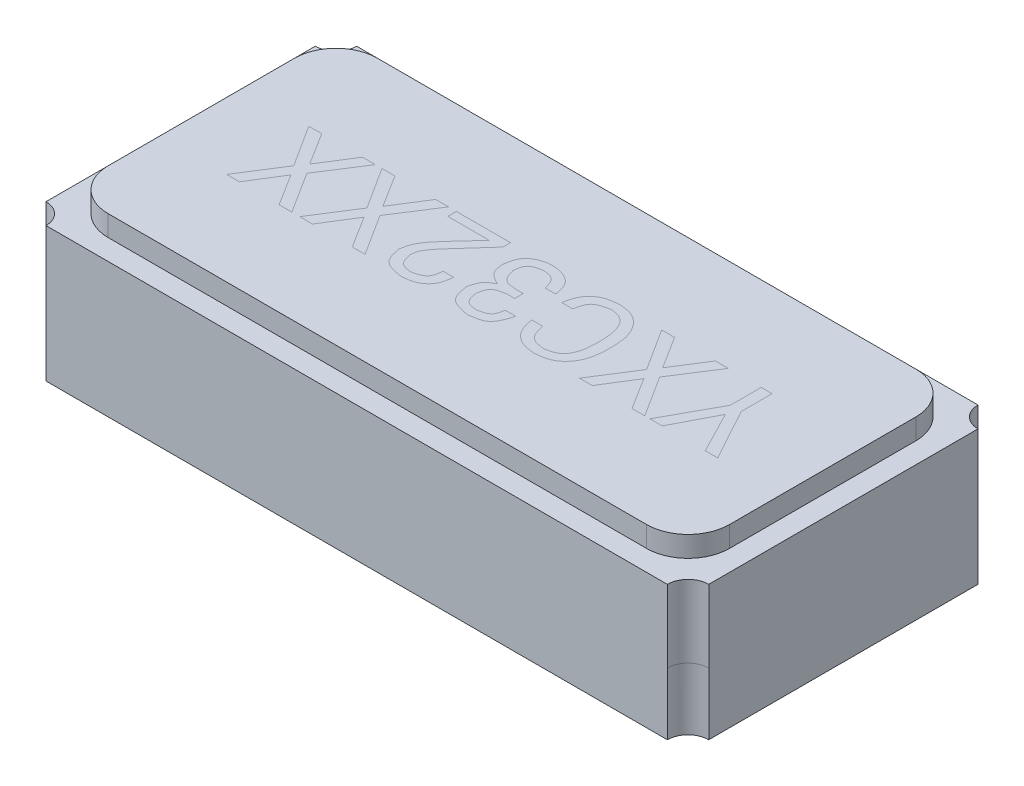
SolidWorks part; units mm, degrees
ref_plane "Спереди" through (0, 0, 0) normal (0, 0, 1) x (1, 0, 0)
ref_plane "Сверху" through (0, 0, 0) normal (0, 1, 0) x (1, 0, 0)
ref_plane "Справа" through (0, 0, 0) normal (1, 0, 0) x (0, 0, -1)
sketch "Эскиз1" plane through (0, 0, 0) normal (0, 1, 0) x (1, 0, 0)
  line L1 (-1.5, 0.75) -> (1.5, 0.75)
  line L2 (-1.6, 0.65) -> (-1.6, -0.65)
  line L3 (-1.5, -0.75) -> (1.5, -0.75)
  line L4 (1.6, 0.65) -> (1.6, -0.65)
  arc A0 (-1.6, 0.65) -> (-1.5, 0.75) centre (-1.6, 0.75) ccw
  arc A1 (1.5, 0.75) -> (1.6, 0.65) centre (1.6, 0.75) ccw
  arc A2 (-1.6, -0.65) -> (-1.5, -0.75) centre (-1.6, -0.75) cw
  arc A3 (1.5, -0.75) -> (1.6, -0.65) centre (1.6, -0.75) cw
  point P0 (0, 0)
  dimension "D3" = 0.1
  dimension "D1" = 3.2
  dimension "D2" = 1.5
  dimension "D4" = 1.6
  dimension "D5" = 0.75
extrude "Бобышка-Вытянуть1" add sketch "Эскиз1" along normal blind 0.65
sketch "Эскиз2" plane through (0, 0.65, 0) normal (0, 1, 0) x (1, 0, 0)
  line L0 (1.5, 0.75) -> (-1.5, 0.75) construction
  line L1 (-1.3, 0.65) -> (1.3, 0.65)
  line L2 (-1.5, 0.45) -> (-1.5, -0.45)
  line L3 (-1.3, -0.65) -> (1.3, -0.65)
  line L4 (1.5, 0.45) -> (1.5, -0.45)
  line L5 (-1.5, -0.75) -> (1.5, -0.75) construction
  line L6 (-1.6, 0.65) -> (-1.6, -0.65) construction
  line L7 (1.6, -0.65) -> (1.6, 0.65) construction
  arc A0 (1.3, -0.65) -> (1.5, -0.45) centre (1.3, -0.45) ccw
  arc A1 (1.3, 0.65) -> (1.5, 0.45) centre (1.3, 0.45) cw
  arc A2 (-1.5, -0.45) -> (-1.3, -0.65) centre (-1.3, -0.45) ccw
  arc A3 (-1.3, 0.65) -> (-1.5, 0.45) centre (-1.3, 0.45) ccw
  dimension "D1" = 0.2
  dimension "D2" = 0.1
  dimension "D3" = 0.1
  dimension "D4" = 0.1
  dimension "D5" = 0.1
extrude "Бобышка-Вытянуть2" add sketch "Эскиз2" along normal blind 0.1
sketch "Эскиз3" plane through (0, 0, 0) normal (0, -1, 0) x (1, 0, 0)
  line L0 (1.5, -0.75) -> (1.4, -0.65)
  line L1 (1.4, -0.65) -> (0.85, -0.65)
  line L2 (0.85, -0.65) -> (0.85, 0.35)
  line L3 (1.15, 0.65) -> (1.4, 0.65)
  line L4 (1.4, 0.65) -> (1.5, 0.75)
  line L5 (1.6, 0.65) -> (1.5, 0.55)
  line L6 (1.5, 0.55) -> (1.5, -0.55)
  line L7 (1.5, -0.55) -> (1.6, -0.65)
  line L8 (1.6, 0.65) -> (1.6, -0.65) construction
  line L9 (1.5, -0.75) -> (-1.5, -0.75) construction
  line L10 (-1.5, 0.75) -> (1.5, 0.75) construction
  line L11 (0, -0.75) -> (0, 0.75) construction
  line L12 (-1.5, -0.55) -> (-1.6, -0.65)
  line L13 (-1.5, 0.55) -> (-1.5, -0.55)
  line L14 (-1.6, 0.65) -> (-1.5, 0.55)
  line L15 (-1.4, 0.65) -> (-1.5, 0.75)
  line L16 (-0.85, 0.65) -> (-1.4, 0.65)
  line L17 (-0.85, -0.65) -> (-0.85, 0.65)
  line L18 (-1.4, -0.65) -> (-0.85, -0.65)
  line L19 (-1.5, -0.75) -> (-1.4, -0.65)
  line L20 (1.15, 0.65) -> (0.85, 0.35)
  arc A0 (1.5, 0.75) -> (1.6, 0.65) centre (1.6, 0.75) ccw
  arc A1 (1.6, -0.65) -> (1.5, -0.75) centre (1.6, -0.75) ccw
  arc A2 (1.6, -0.65) -> (1.5, -0.75) centre (1.6, -0.75) ccw construction
  arc A3 (1.5, 0.75) -> (1.6, 0.65) centre (1.6, 0.75) ccw construction
  arc A4 (-1.5, 0.75) -> (-1.6, 0.65) centre (-1.6, 0.75) cw
  arc A5 (-1.6, -0.65) -> (-1.5, -0.75) centre (-1.6, -0.75) cw
  dimension "D1" = 45
  dimension "D2" = 0.1
  dimension "D3" = 0.1
  dimension "D4" = 0.1
  dimension "D5" = 135
  dimension "D6" = 0.65
  dimension "D7" = 135
  dimension "D8" = 0.3
wrap "Перенос1" sketch "Эскиз3" wrap type scribe source sketch "Эскиз3"
sketch "Эскиз4" plane through (0, 0, -0.75) normal (0, 0, -1) x (-1, 0, 0)
  line L0 (-1.6, 0.3) -> (1.6, 0.3)
  line L1 (-1.6, 0.65) -> (-1.6, 0) construction
  line L2 (1.6, 0.65) -> (1.6, 0) construction
  line L3 (-1.5, 0) -> (1.5, 0) construction
  point P2 (0, 0)
  point P5 (0, 0)
  dimension "D1" = 0.3
split line "Разделяющая линия1"
sketch "Эскиз5" plane through (0, 0.75, 0) normal (0, 1, 0) x (1, 0, 0)
  line L0 (-1.5, 0.2) -> (1.5, 0.2) construction
  line L1 (-1.5, 0.45) -> (-1.5, -0.45) construction
  line L2 (1.5, -0.45) -> (1.5, 0.45) construction
  line L6 (1.5, 0.75) -> (-1.5, 0.75) construction
  text T0 "YXC32XX" font "Roboto" height 0.4
  point P4 (-1.3138, -0.3283)
  point P7 (0, 0)
  dimension "D1" = 0.55
wrap "Перенос2" sketch "Эскиз5" wrap type scribe source sketch "Эскиз5"
equation "\"D4@Эскиз2\"=\"D2@Эскиз2\""
equation "\"D3@Эскиз2\"=\"D2@Эскиз2\""
equation "\"D5@Эскиз2\"=\"D2@Эскиз2\""
